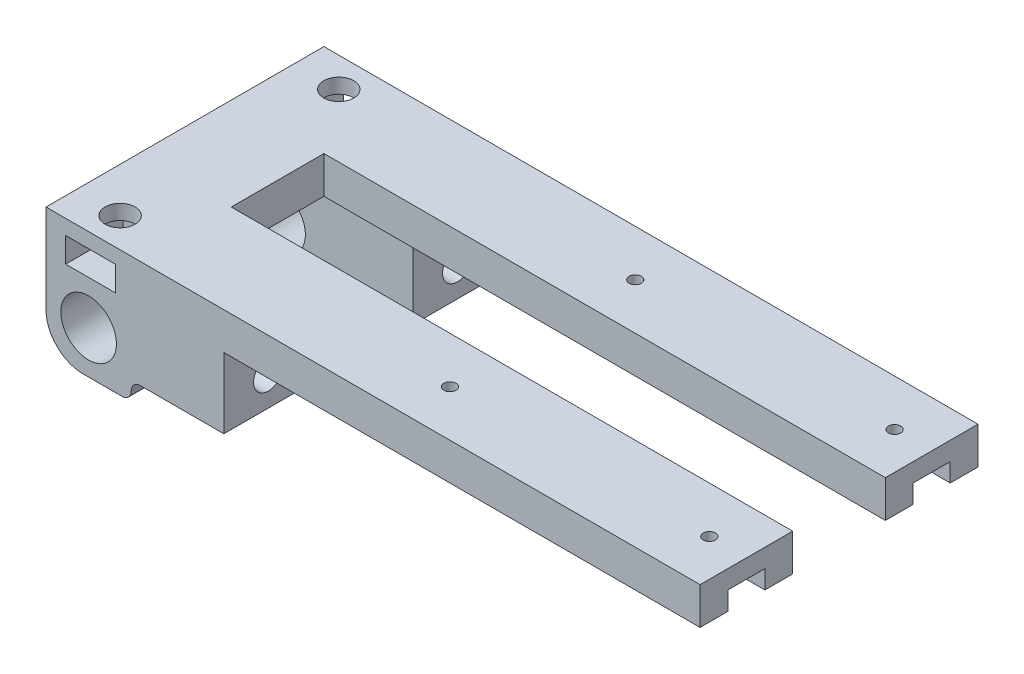
SolidWorks part; units mm, degrees
ref_plane "Front Plane" through (0, 0, 0) normal (0, 0, 1) x (1, 0, 0)
ref_plane "Top Plane" through (0, 0, 0) normal (0, 1, 0) x (1, 0, 0)
ref_plane "Right Plane" through (0, 0, 0) normal (1, 0, 0) x (0, 0, -1)
sketch "Sketch1" plane through (0, 0, 0) normal (0, 1, 0) x (1, 0, 0)
  line L0 (-108.6427, -967.1912) -> (-108.6427, 49032.8088) construction
  line L1 (-120.1427, 45.9408) -> (56.3573, 45.9408)
  line L2 (-120.1427, 45.9408) -> (-120.1427, -29.0592)
  line L3 (-120.1427, -29.0592) -> (56.3573, -29.0592)
  line L4 (56.3573, 45.9408) -> (56.3573, 20.9408)
  line L5 (56.3573, -4.0592) -> (56.3573, -29.0592)
  line L6 (-95.1427, 20.9408) -> (56.3573, 20.9408)
  line L7 (-95.1427, 20.9408) -> (-95.1427, -4.0592)
  line L8 (-95.1427, -4.0592) -> (56.3573, -4.0592)
  line L10 (-116.1427, 45.9408) -> (-101.1427, 45.9408) construction
  line L11 (-116.1427, 45.9408) -> (-116.1427, 21.9408) construction
  line L12 (-116.1427, 21.9408) -> (-101.1427, 21.9408) construction
  line L13 (-101.1427, 45.9408) -> (-101.1427, 21.9408) construction
  dimension "D1" = 165
  dimension "D2" = 15
  dimension "D3" = 24
  dimension "D4" = 75
  dimension "D5" = 4
  dimension "D6" = 25
  dimension "D7" = 25
extrude "Boss-Extrude1" add sketch "Sketch1" along normal blind 10
sketch "Sketch2" plane through (0, 0, 0) normal (0, 1, 0) x (1, 0, 0)
  line L0 (56.3573, 20.9408) -> (56.3573, 45.9408) construction
  line L1 (-33.6427, 38.4408) -> (56.3573, 38.4408)
  line L2 (-33.6427, 38.4408) -> (-33.6427, 28.4408)
  line L3 (-33.6427, 28.4408) -> (56.3573, 28.4408)
  line L4 (56.3573, 38.4408) -> (56.3573, 28.4408)
  line L5 (-1148.8504, 33.4408) -> (48851.1496, 33.4408) construction
  line L6 (-1164.3604, -16.5592) -> (48835.6396, -16.5592) construction
  line L7 (56.3573, 45.9408) -> (-120.1427, 45.9408) construction
  line L8 (-95.1427, 20.9408) -> (56.3573, 20.9408) construction
  line L9 (56.3573, -4.0592) -> (-95.1427, -4.0592) construction
  line L10 (-120.1427, -29.0592) -> (56.3573, -29.0592) construction
  line L11 (56.3573, -29.0592) -> (56.3573, -4.0592) construction
  line L12 (-33.6427, -11.5592) -> (56.3573, -11.5592)
  line L13 (-33.6427, -11.5592) -> (-33.6427, -21.5592)
  line L14 (-33.6427, -21.5592) -> (56.3573, -21.5592)
  line L15 (56.3573, -11.5592) -> (56.3573, -21.5592)
  dimension "D1" = 10
  dimension "D2" = 90
extrude "Cut-Extrude1" cut sketch "Sketch2" along normal blind 5
sketch "Sketch3" plane through (0, 5, 0) normal (0, -1, 0) x (-1, 0, 0)
  line L0 (-1033.6427, 33.4408) -> (48966.3573, 33.4408) construction
  line L1 (33.6427, 38.4408) -> (33.6427, 28.4408) construction
  line L2 (-1033.6427, -16.5592) -> (48966.3573, -16.5592) construction
  line L3 (33.6427, -11.5592) -> (33.6427, -21.5592) construction
  line L6 (33.6427, -11.5592) -> (33.6427, -21.5592) construction
  line L7 (-56.3573, -21.5592) -> (-56.3573, -11.5592) construction
  circle A0 centre (23.6427, 33.4408) radius 1.65
  circle A1 centre (-46.3573, 33.4408) radius 1.65
  circle A2 centre (23.6427, -16.5592) radius 1.65
  circle A3 centre (-46.3573, -16.5592) radius 1.65
  point P5 (33.6427, 33.4408)
  point P10 (33.6427, -16.5592)
  dimension "D1" = 3.3
  dimension "D2" = 10
  dimension "D3" = 10
extrude "Cut-Extrude2" cut sketch "Sketch3" against normal through all
sketch "Sketch5" plane through (0, 0, 0) normal (0, -1, 0) x (1, 0, 0)
  line L0 (-120.1427, -45.9408) -> (-120.1427, 29.0592) construction
  line L1 (-120.1427, 29.0592) -> (-97.1427, 29.0592)
  line L2 (-120.1427, 29.0592) -> (-120.1427, 5.0592)
  line L3 (-120.1427, 5.0592) -> (-97.1427, 5.0592)
  line L4 (-97.1427, 29.0592) -> (-97.1427, 5.0592)
  line L5 (-120.1427, -45.9408) -> (-97.1427, -45.9408)
  line L6 (-120.1427, -45.9408) -> (-120.1427, -21.9408)
  line L7 (-120.1427, -21.9408) -> (-97.1427, -21.9408)
  line L8 (-97.1427, -45.9408) -> (-97.1427, -21.9408)
  line L9 (56.3573, -45.9408) -> (-120.1427, -45.9408) construction
  dimension "D1" = 23
  dimension "D2" = 24
extrude "Boss-Extrude2" add sketch "Sketch5" along normal blind 24
sketch "Sketch6" plane through (0, 0, 29.0592) normal (0, 0, 1) x (1, 0, 0)
  line L0 (-108.6427, -1016) -> (-108.6427, 48984) construction
  line L1 (-97.1427, -24) -> (-120.1427, -24) construction
  circle A0 centre (-108.6427, -12.5) radius 7.5
  point P5 (-108.6427, -24)
  dimension "D1" = 15
  dimension "D2" = 4
extrude "Cut-Extrude3" cut sketch "Sketch6" against normal through all
sketch "Sketch7" plane through (0, 0, 0) normal (0, -1, 0) x (1, 0, 0)
  line L0 (56.3573, -45.9408) -> (-97.1427, -45.9408) construction
  line L1 (-72.1427, -45.9408) -> (-97.1427, -45.9408)
  line L2 (-72.1427, -45.9408) -> (-72.1427, -21.9408)
  line L3 (-72.1427, -21.9408) -> (-97.1427, -21.9408)
  line L4 (-97.1427, -45.9408) -> (-97.1427, -21.9408)
  line L5 (-97.1427, -21.9408) -> (-120.1427, -21.9408) construction
  line L6 (-97.1427, -45.9408) -> (-97.1427, -21.9408) construction
  line L7 (-120.1427, 5.0592) -> (-97.1427, 5.0592) construction
  line L8 (-97.1427, 29.0592) -> (-72.1427, 29.0592)
  line L9 (-97.1427, 29.0592) -> (-97.1427, 5.0592)
  line L10 (-97.1427, 5.0592) -> (-72.1427, 5.0592)
  line L11 (-72.1427, 29.0592) -> (-72.1427, 5.0592)
  dimension "D1" = 25
extrude "Boss-Extrude3" add sketch "Sketch7" along normal blind 19
sketch "Sketch8" plane through (-72.1427, 0, 0) normal (-1, 0, 0) x (0, 0, 1)
  line L0 (17.0592, -1021) -> (17.0592, 48979) construction
  line L1 (29.0592, -24) -> (5.0592, -24) construction
  line L2 (-33.9408, -1021) -> (-33.9408, 48979) construction
  line L3 (-21.9408, -24) -> (-45.9408, -24) construction
  line L9 (5.0592, -19) -> (29.0592, -19) construction
  circle A0 centre (17.0592, -11) radius 7.5 construction
  circle A1 centre (-33.9408, -11) radius 4
  circle A2 centre (17.0592, -11) radius 4
  point P9 (17.0592, -24)
  point P14 (-33.9408, -24)
  dimension "D1" = 15
  dimension "D2" = 4
  dimension "D3" = 8
extrude "Cut-Extrude4" cut sketch "Sketch8" along normal offset from surface (25 mm away) 23 up to face at (-120.1427, -11, -10.1283)
fillet "Fillet2" radius 10 2 edges at (-120.1427, -24, 17.0592) (-120.1427, -24, -33.9408)
sketch "Sketch12" plane through (0, 0, -45.9408) normal (0, 0, -1) x (-1, 0, 0)
  line L0 (-56.3573, 10) -> (120.1427, 10) construction
  line L1 (101.4427, 6) -> (114.8427, 6)
  line L2 (101.4427, 6) -> (101.4427, -0.7)
  line L3 (101.4427, -0.7) -> (114.8427, -0.7)
  line L4 (114.8427, 6) -> (114.8427, -0.7)
  line L5 (108.1427, -994) -> (108.1427, 49006) construction
  line L6 (120.1427, 10) -> (120.1427, -14) construction
  point P9 (108.1427, 6)
  dimension "D1" = 6.7
  dimension "D2" = 4
  dimension "D3" = 13.4
  dimension "D4" = 12
extrude "Cut-Extrude5" cut sketch "Sketch12" against normal blind 15.5
extrude "Cut-Extrude6" cut sketch "Sketch12<2>" along normal blind 15.5 from surface starting at face at (-71.4005, -9.3968, 29.0592)
sketch "Sketch12<2>" plane through (0, 0, -45.9408) normal (0, 0, -1) x (-1, 0, 0) same geometry as "Sketch12"
sketch "Sketch13" plane through (0, 10, 0) normal (0, 1, 0) x (1, 0, 0)
  line L0 (56.3573, 45.9408) -> (-120.1427, 45.9408) construction
  line L1 (-120.1427, 45.9408) -> (-120.1427, -29.0592) construction
  line L2 (-1120.1427, 8.4408) -> (48879.8573, 8.4408) construction
  circle A0 centre (-108.1427, 37.9408) radius 11 construction
  circle A1 centre (-108.1427, 37.9408) radius 4.05
  circle A2 centre (-108.1427, -21.0592) radius 4.05
  point P12 (-120.1427, 8.4408)
  dimension "D1" = 22
  dimension "D2" = 8.1
  dimension "D3" = 3.95
  dimension "D4" = 12
extrude "Cut-Extrude7" cut sketch "Sketch13" against normal up to next
fillet "Fillet3" radius 2.5 4 edges at (-97.1427, -19, -33.9408) (-97.1427, -24, -33.9408) (-97.1427, -19, 17.0592) (-97.1427, -24, 17.0592)
